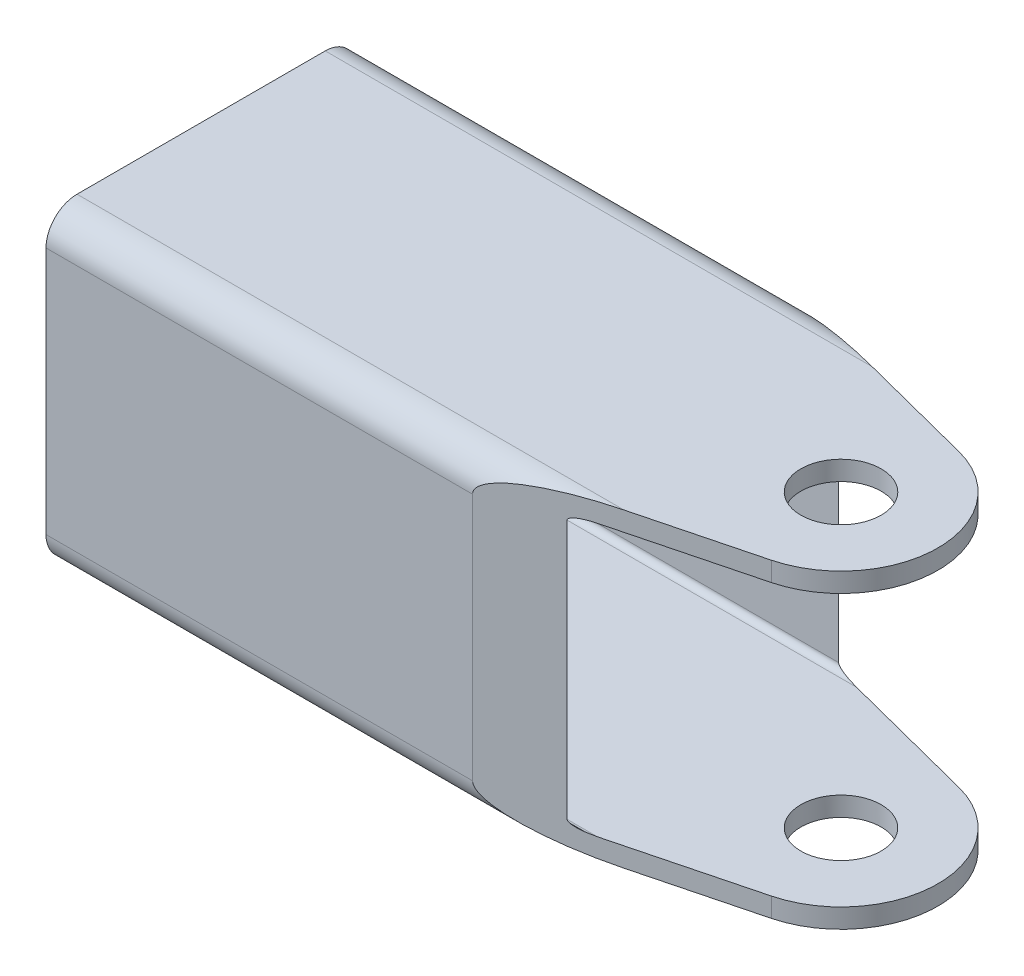
SolidWorks part; units mm, degrees
material "AISI 4130 Steel, annealed at 865C"
ref_plane "Front Plane" through (0, 0, 0) normal (0, 0, 1) x (1, 0, 0)
ref_plane "Top Plane" through (0, 0, 0) normal (0, 1, 0) x (1, 0, 0)
ref_plane "Right Plane" through (0, 0, 0) normal (1, 0, 0) x (0, 0, -1)
sketch "Sketch1" plane through (0, 0, 0) normal (1, 0, 0) x (0, 0, -1)
  line L1 (-10.16, 12.7) -> (10.16, 12.7)
  line L2 (-12.7, 10.16) -> (-12.7, -10.16)
  line L3 (-10.16, -12.7) -> (10.16, -12.7)
  line L4 (12.7, 10.16) -> (12.7, -10.16)
  arc A0 (-10.16, 12.7) -> (-12.7, 10.16) centre (-10.16, 10.16) ccw
  arc A1 (-10.16, -12.7) -> (-12.7, -10.16) centre (-10.16, -10.16) cw
  arc A2 (10.16, 12.7) -> (12.7, 10.16) centre (10.16, 10.16) cw
  arc A3 (12.7, -10.16) -> (10.16, -12.7) centre (10.16, -10.16) cw
  point P4 (0, -12.7)
  point P7 (0, 0)
  point P15 (12.7, 0)
  dimension "D3" = 2.54
  dimension "D4" = 2.54
  dimension "D5" = 2.54
  dimension "D6" = 2.54
  dimension "D1" = 25.4
  dimension "D2" = 20.32
extrude "Boss-Extrude1" add sketch "Sketch1" along normal blind 25.4 and the other way blind 34.925
sketch "Sketch11" plane through (25.4, 0, 0) normal (1, 0, 0) x (0, 0, -1)
  line L0 (-10.16, -12.7) -> (10.16, -12.7) construction
  line L1 (-10.6045, 11.1125) -> (10.6045, 11.1125)
  line L2 (-11.1125, 10.6045) -> (-11.1125, -10.6045)
  line L3 (-10.6045, -11.1125) -> (10.6045, -11.1125)
  line L4 (11.1125, 10.6045) -> (11.1125, -10.6045)
  line L5 (10.16, 12.7) -> (-10.16, 12.7) construction
  line L6 (12.7, -10.16) -> (12.7, 10.16) construction
  line L7 (-12.7, 10.16) -> (-12.7, -10.16) construction
  arc A0 (10.6045, 11.1125) -> (11.1125, 10.6045) centre (10.6045, 10.6045) cw
  arc A1 (10.6045, -11.1125) -> (11.1125, -10.6045) centre (10.6045, -10.6045) ccw
  arc A2 (-11.1125, -10.6045) -> (-10.6045, -11.1125) centre (-10.6045, -10.6045) ccw
  arc A3 (-10.6045, 11.1125) -> (-11.1125, 10.6045) centre (-10.6045, 10.6045) ccw
  dimension "D1" = 1.5875
  dimension "D2" = 1.5875
  dimension "D3" = 1.5875
  dimension "D4" = 1.5875
  dimension "D5" = 0.508
extrude "Cut-Extrude4" cut sketch "Sketch11" against normal through all
sketch "Sketch12" plane through (0, 12.7, 0) normal (0, 1, 0) x (1, 0, 0)
  line L1 (0, 12.7) -> (50.8, 12.7)
  line L2 (50.8, 12.7) -> (50.8, -12.7)
  line L12 (50.8, -12.7) -> (0, -12.7)
  line L13 (19.4444, -7.6861) -> (0, -12.7)
  line L14 (19.4444, 7.6861) -> (0, 12.7)
  line L15 (-34.925, -12.7) -> (25.4, -12.7) construction
  line L16 (-34.925, 12.7) -> (25.4, 12.7) construction
  line L18 (25.4, 10.16) -> (25.4, -10.16) construction
  arc A1 (19.4444, -7.6861) -> (19.4444, 7.6861) centre (17.4625, 0) ccw
  point P8 (18.1688, 9.2165)
  line M6 (-34.925, -10.16) -> (25.4, -10.16)
  line M7 (25.4, -10.16) -> (25.4, 10.16)
  line M8 (25.4, 10.16) -> (-34.925, 10.16)
  line M9 (-34.925, 10.16) -> (-34.925, -10.16)
  dimension "D2" = 50.8
  dimension "D1" = 17.4625
extrude "Cut-Extrude5" cut sketch "Sketch12" against normal through all contours M9 M8 M7 M6 | M7 M8 M9 | M6 M7 region at (34.888, 12.7, 0) region at (20.955, 12.7, -8.1283) region at (20.955, 12.7, 8.1283)
sketch "Sketch14" plane through (0, 12.7, 0) normal (0, 1, 0) x (1, 0, 0)
  circle A0 centre (17.4625, 0) radius 3.2893
  arc A2 (19.4444, -7.6861) -> (19.4444, 7.6861) centre (17.4625, 0) ccw construction
  point P0 (17.4625, 0)
  point P6 (25.4, 0)
  dimension "D2" = 6.5786
  dimension "D1" = 7.9375
  dimension "D3" = 17.4625
extrude "Cut-Extrude6" cut sketch "Sketch14" against normal through all
